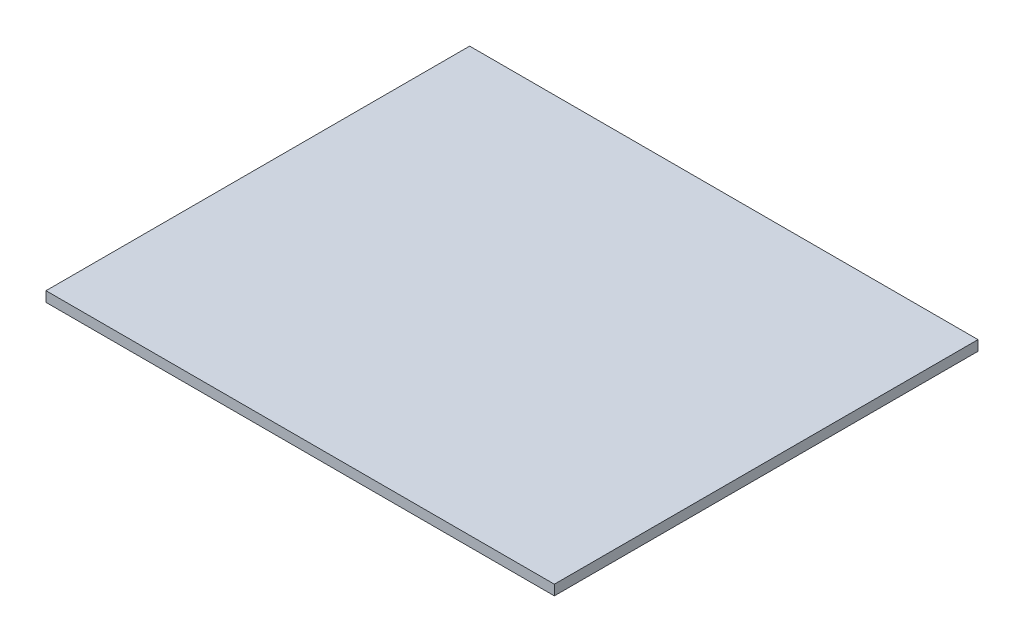
SolidWorks part; units mm, degrees
ref_plane "Front Plane" through (0, 0, 0) normal (0, 0, 1) x (1, 0, 0)
ref_plane "Top Plane" through (0, 0, 0) normal (0, 1, 0) x (1, 0, 0)
ref_plane "Right Plane" through (0, 0, 0) normal (1, 0, 0) x (0, 0, -1)
sketch "Sketch1" plane through (0, 0, 0) normal (0, 1, 0) x (1, 0, 0)
  line L1 (-457.2, -381) -> (457.2, -381)
  line L2 (-457.2, -381) -> (-457.2, 381)
  line L3 (-457.2, 381) -> (457.2, 381)
  line L4 (457.2, -381) -> (457.2, 381)
  line L5 (-457.2, -381) -> (457.2, 381) construction
  line L6 (-457.2, 381) -> (457.2, -381) construction
  point P0 (0, 0)
  dimension "D1" = 762
  dimension "D2" = 914.4
extrude "Boss-Extrude1" add sketch "Sketch1" along normal blind 18.2562
